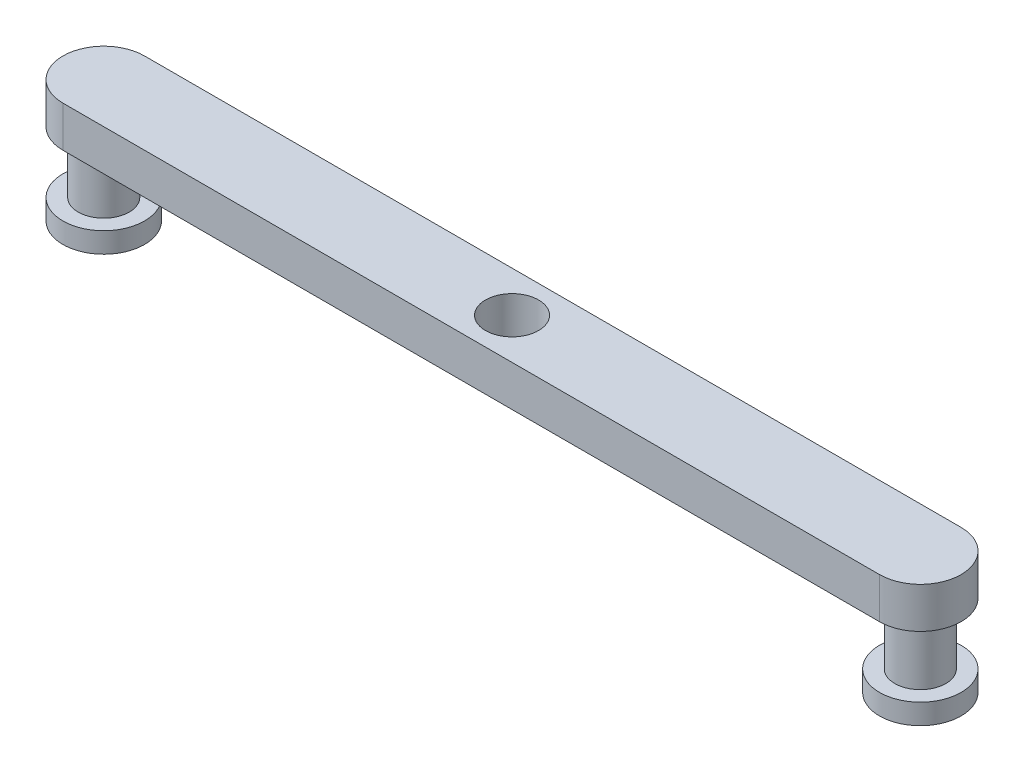
SolidWorks part; units mm, degrees
ref_plane "Front Plane" through (0, 0, 0) normal (0, 0, 1) x (1, 0, 0)
ref_plane "Top Plane" through (0, 0, 0) normal (0, 1, 0) x (1, 0, 0)
ref_plane "Right Plane" through (0, 0, 0) normal (1, 0, 0) x (0, 0, -1)
sketch "Sketch1" plane through (0, 0, 0) normal (0, 1, 0) x (1, 0, 0)
  line L0 (0, 0) -> (-50.8, 0)
  line L1 (0, 0) -> (50.8, 0)
  line L2 (-50.8, -5.08) -> (50.8, -5.08)
  line L3 (-50.8, 5.08) -> (50.8, 5.08)
  arc A0 (-50.8, 5.08) -> (-50.8, -5.08) centre (-50.8, 0) ccw
  arc A1 (50.8, -5.08) -> (50.8, 5.08) centre (50.8, 0) ccw
  dimension "D1" = 101.6
sketch "Sketch2" plane through (0, 0, 0) normal (0, 1, 0) x (1, 0, 0)
  line L0 (-50.8, -5.08) -> (50.8, -5.08)
  line L1 (-50.8, 5.08) -> (50.8, 5.08)
  arc A0 (-50.8, 5.08) -> (-50.8, -5.08) centre (-50.8, 0) ccw
  arc A1 (50.8, -5.08) -> (50.8, 5.08) centre (50.8, 0) ccw
extrude "Boss-Extrude1" add sketch "Sketch2" along normal blind 5.08
sketch "Sketch3" plane through (0, 0, 0) normal (0, -1, 0) x (1, 0, 0)
  circle A0 centre (-50.8, 0) radius 3.175
  circle A1 centre (50.8, 0) radius 3.175
extrude "Boss-Extrude2" add sketch "Sketch3" along normal blind 7.62
sketch "Sketch4" plane through (0, -7.62, 0) normal (0, -1, 0) x (1, 0, 0)
  circle A0 centre (-50.8, 0) radius 5.08
  circle A1 centre (50.8, 0) radius 5.08
extrude "Boss-Extrude3" add sketch "Sketch4" along normal blind 2.54
sketch "Sketch5" plane through (0, 0, 0) normal (0, 1, 0) x (1, 0, 0)
  circle A0 centre (0, 0) radius 3.302
sketch "Sketch7" plane through (0, 0, 0) normal (0, 1, 0) x (1, 0, 0)
  circle A0 centre (0, 0) radius 3.302
extrude "Cut-Extrude1" cut sketch "Sketch7" along normal up to vertex (5.08 mm away) up to point (-50.8, 5.08, 5.08)
